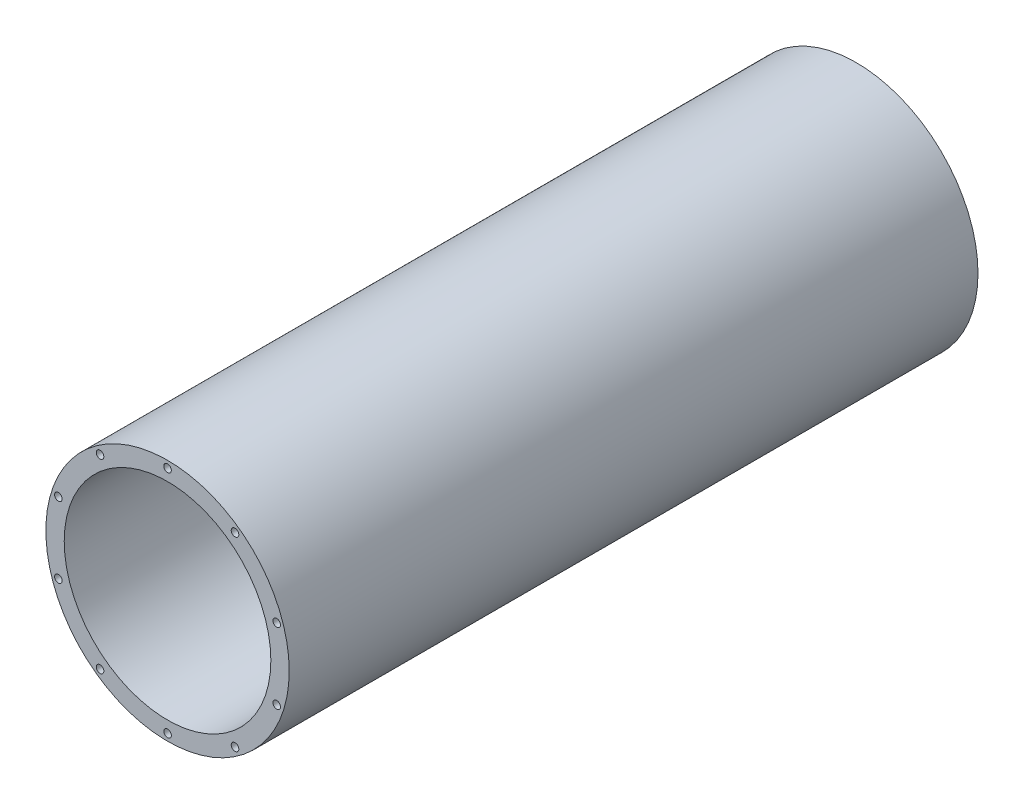
SolidWorks part; units mm, degrees
ref_plane "前视基准面" through (0, 0, 0) normal (0, 0, 1) x (1, 0, 0)
ref_plane "上视基准面" through (0, 0, 0) normal (0, 1, 0) x (1, 0, 0)
ref_plane "右视基准面" through (0, 0, 0) normal (1, 0, 0) x (0, 0, -1)
sketch "草图1" plane through (0, 0, 0) normal (0, 0, 1) x (1, 0, 0)
  circle A0 centre (0, 0) radius 53
  dimension "D1" = 106
extrude "凸台-拉伸1" add sketch "草图1" along normal blind 300
sketch "草图2" plane through (0, 0, 0) normal (0, 0, -1) x (-1, 0, 0)
  circle A0 centre (0, 0) radius 45
  dimension "D1" = 90
extrude "切除-拉伸1" cut sketch "草图2" against normal blind 300
hole_wizard "M4 螺纹孔1" positions "草图4" profile "草图3" tap size "M4" standard "GB"
sketch "草图4" plane through (0, 0, 0) normal (0, 0, -1) x (-1, 0, 0)
  line L0 (0, 0) -> (0, 60.9486) construction
  circle A0 centre (0, 0) radius 50 construction
  point P0 (0, 50)
  dimension "D1" = 100
sketch "草图3" plane through (0, 50, 0) normal (1, 0, 0) x (0, 1, 0)
  line L0 (0, 0) -> (0, 11.0914)
  line L1 (0, 11.0914) -> (1.65, 10.1)
  line L2 (1.65, 10.1) -> (1.65, 0)
  line L5 (1.65, 0) -> (0, 0)
  line L10 (0, 11.0914) -> (-1.65, 10.1) construction
  line L11 (0, -6.35) -> (0, 107.95) construction
  dimension "螺纹孔钻头直径" = 3.3
  dimension "螺纹孔钻头深度" = 10.1
  dimension "导头角度" = 118
cosmetic thread "孔螺蚊线1" parameters "D1"=8, "D2"=4
ref_axis "基准轴1" through (0, 0, 300) along (0, 0, -1)
pattern_circular "阵列(圆周)1" count 10 over 360 about axis through (0, 0, 300) along (0, 0, -1) of "M4 螺纹孔1"
hole_wizard "M4 螺纹孔2" positions "草图6" profile "草图5" tap size "M4" standard "GB"
sketch "草图6" plane through (0, 0, 300) normal (0, 0, 1) x (1, 0, 0)
  line L0 (0, 0) -> (0, 56.8506) construction
  circle A0 centre (0, 0) radius 50 construction
  point P0 (0, 50)
  dimension "D1" = 100
sketch "草图5" plane through (0, 50, 300) normal (1, 0, 0) x (0, -1, 0)
  line L0 (0, 0) -> (0, 11.0914)
  line L1 (0, 11.0914) -> (1.65, 10.1)
  line L2 (1.65, 10.1) -> (1.65, 0)
  line L5 (1.65, 0) -> (0, 0)
  line L10 (0, 11.0914) -> (-1.65, 10.1) construction
  line L11 (0, -6.35) -> (0, 107.95) construction
  dimension "螺纹孔钻头直径" = 3.3
  dimension "螺纹孔钻头深度" = 10.1
  dimension "导头角度" = 118
cosmetic thread "孔螺蚊线2" parameters "D1"=8, "D2"=4
pattern_circular "阵列(圆周)2" count 10 over 360 about axis through (0, 0, 300) along (0, 0, -1) of "M4 螺纹孔2"
